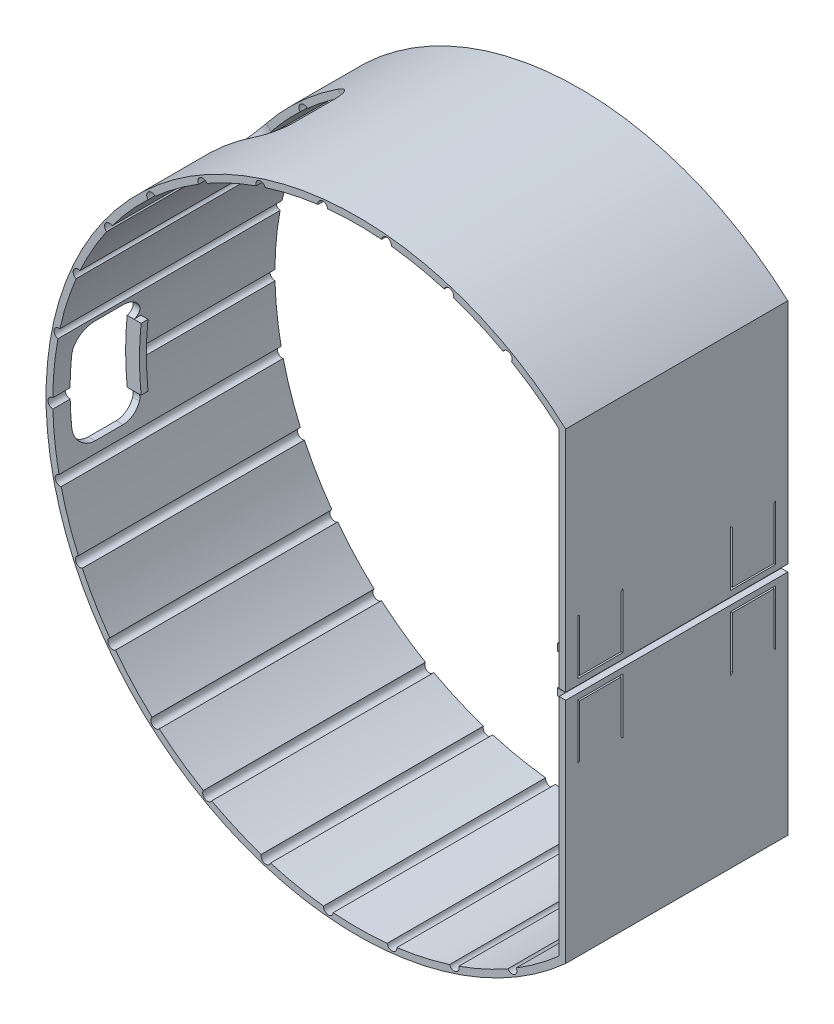
SolidWorks part; units mm, degrees
ref_plane "Front Plane" through (0, 0, 0) normal (1, 0, 0) x (0, 1, 0)
ref_plane "Top Plane" through (0, 0, 0) normal (0, 0, 1) x (0, 1, 0)
ref_plane "Right Plane" through (0, 0, 0) normal (0, 1, 0) x (-1, 0, 0)
sketch "Sketch1" plane through (0, 0, 0) normal (0, 0, 1) x (0, 1, 0)
  line L0 (-66.9026, -60.2) -> (-1, -60.2)
  line L1 (-65.9842, -58.3) -> (-1, -58.3)
  line L2 (-1, -60.2) -> (-1, -58.3)
  line L3 (1, -60.2) -> (1, -58.3)
  line L4 (1, -60.2) -> (66.9026, -60.2)
  line L5 (1, -58.3) -> (65.9842, -58.3)
  arc A0 (66.9026, -60.2) -> (-66.9026, -60.2) centre (0, 0) ccw
  arc A1 (65.9842, -58.3) -> (-65.9842, -58.3) centre (0, 0) ccw
  dimension "D1" = 180
  dimension "D2" = 176.1
  dimension "D3" = 60.2
  dimension "D4" = 1.9
  dimension "D5" = 1
  dimension "D6" = 1
extrude "Boss-Extrude1" add sketch "Sketch1" along normal blind 64.2
sketch "Sketch2" plane through (0, 0, 0) normal (1, 0, 0) x (0, 1, 0)
  line L0 (0, 67.3305) -> (0, -7.6543) construction
ref_plane "Plane1" through (0, 0, 0) normal (0.7071, -0.7071, 0) x (0, 0, -1)
sketch "Sketch3" plane through (0, 0, 0) normal (0.7071, -0.7071, 0) x (0, 0, -1)
  line L0 (-64.2, 87.8822) -> (-64.2, -88.05) construction
  line L1 (-44.2, -16.05) -> (-20.2, -16.05)
  line L2 (-44.2, -16.05) -> (-44.2, 23.95)
  line L3 (-44.2, 23.95) -> (-20.2, 23.95)
  line L4 (-20.2, -16.05) -> (-20.2, 23.95)
  line L6 (-64.2, -88.05) -> (0, -88.05) construction
  dimension "D1" = 40
  dimension "D2" = 24
  dimension "D3" = 20
  dimension "D4" = 72
extrude "Cut-Extrude1" cut sketch "Sketch3" against normal blind 120.2
sketch "Sketch4" plane through (0, 0, 0) normal (1, 0, 0) x (0, 1, 0)
  line L0 (0, 200067.3305) -> (0, -200007.6543) construction
  line L1 (-15, 59.2) -> (15, 59.2)
  line L2 (-15, 59.2) -> (-15, 39.2)
  line L3 (-15, 39.2) -> (15, 39.2)
  line L4 (15, 59.2) -> (15, 39.2)
  line L5 (90, 64.2) -> (-90, 64.2) construction
  dimension "D1" = 15
  dimension "D2" = 15
  dimension "D3" = 20
  dimension "D4" = 5
extrude "Cut-Extrude2" cut sketch "Sketch4" against normal blind 120.2
fillet "Fillet1" radius 6 8 edges at (-43.6939, 77.5643, 44.2) (-73.2676, 50.5695, 44.2) (-73.2676, 50.5695, 20.2) (-43.6939, 77.5643, 20.2) (-87.7521, 15, 39.2) (-87.7521, -15, 39.2) (-87.7521, -15, 59.2) (-87.7521, 15, 59.2)
sketch "Sketch5" plane through (58.3, 0, 0) normal (-1, 0, 0) x (0, -1, 0)
  line L0 (90, 64.2) -> (-90, 64.2) construction
  line L5 (-6.5842, 58.7) -> (-4.5842, 58.7)
  line L6 (-6.5842, 58.7) -> (-6.5842, 49.7)
  line L7 (-6.5842, 49.7) -> (-4.5842, 49.7)
  line L8 (-4.5842, 58.7) -> (-4.5842, 49.7)
  line L9 (-6.5842, 58.7) -> (-4.5842, 49.7) construction
  line L10 (-6.5842, 49.7) -> (-4.5842, 58.7) construction
  line L11 (-65.9842, 64.2) -> (-65.9842, 0) construction
  line L12 (-65.9842, 32.1) -> (65.9842, 32.1) construction
  line L13 (65.9842, 64.2) -> (65.9842, 0) construction
  point P0 (-5.5842, 54.2)
  dimension "D1" = 2
  dimension "D2" = 9
  dimension "D3" = 10
  dimension "D4" = 60.4
extrude "Boss-Extrude2" add sketch "Sketch5" along normal blind 6
sketch "Sketch6" plane through (0, 0, 58.7) normal (0, 0, 1) x (1, 0, 0)
  line L0 (58.3, 6.5842) -> (56.1, 6.5842) construction
  line L1 (52.3, 6.5842) -> (58.3, 6.5842) construction
  line L2 (56.1, 6.5842) -> (56.1, 7.5842)
  line L3 (52.3, 6.5842) -> (56.1, 7.5842)
  line L4 (52.3, 6.5842) -> (56.1, 6.5842)
  dimension "D1" = 1
extrude "Boss-Extrude3" add sketch "Sketch6" against normal blind 9
sketch "Sketch7" plane through (58.3, 0, 0) normal (-1, 0, 0) x (0, -1, 0)
  line L0 (-4.5842, 58.7) -> (-6.5842, 58.7) construction
  line L1 (-18.1626, 60.2) -> (-3.1626, 60.2)
  line L3 (-18.1626, 48.2) -> (-3.1626, 48.2)
  line L4 (-3.1626, 60.2) -> (-3.1626, 48.2)
  line L5 (-18.1626, 60.2) -> (-3.1626, 48.2) construction
  line L6 (-18.1626, 48.2) -> (-3.1626, 60.2) construction
  line L8 (-2.6626, 60.7) -> (-18.6626, 60.7)
  line L9 (-2.6626, 60.7) -> (-2.6626, 47.7)
  line L10 (-2.6626, 47.7) -> (-18.6626, 47.7)
  line L12 (-2.6626, 60.7) -> (-18.6626, 47.7) construction
  line L13 (-2.6626, 47.7) -> (-18.6626, 60.7) construction
  line L14 (-18.1626, 60.2) -> (-18.6626, 60.7)
  line L15 (-18.1626, 48.2) -> (-18.6626, 47.7)
  point P0 (-10.6626, 54.2)
  point P7 (-10.6626, 54.2)
  dimension "D1" = 12
  dimension "D2" = 15
  dimension "D3" = 1.5
  dimension "D4" = 0.5
  dimension "D5" = 0.5
extrude "Cut-Extrude3" cut sketch "Sketch7" against normal blind 9
sketch "Sketch8" plane through (58.3, 0, 0) normal (-1, 0, 0) x (0, -1, 0)
  line L0 (0, 74.2736) -> (0, -25.5173) construction
  line L1 (0, 200067.3305) -> (0, -200007.6543) construction
  line L2 (-65.9842, 32.1) -> (101.8942, 32.1) construction
  line L3 (-65.9842, 64.2) -> (-65.9842, 0) construction
ref_plane "Plane2" through (0, 0, 0) normal (0, 1, 0) x (-1, 0, 0)
ref_plane "Plane3" through (0, 0, 32.1) normal (0, 0, 1) x (0, -1, 0)
mirror "Mirror1" about plane through (0, 0, 0) normal (0, 1, 0) of "Cut-Extrude3", "Boss-Extrude3", "Boss-Extrude2"
mirror "Mirror2" about plane through (0, 0, 32.1) normal (0, 0, 1) of "Mirror1", "Cut-Extrude3", "Boss-Extrude3", "Boss-Extrude2"
sketch "Sketch9" plane through (0, 0, 64.2) normal (0, 0, 1) x (1, 0, 0)
  circle A0 centre (-88.0464, -0.7976) radius 1.4
  arc A1 (58.3, 65.9842) -> (58.3, -65.9842) centre (0, 0) ccw construction
  circle A2 centre (-86.2882, 17.5257) radius 1.4
  circle A3 centre (-80.7588, 35.083) radius 1.4
  circle A4 centre (-71.6998, 51.1071) radius 1.4
  circle A5 centre (-59.5073, 64.8975) radius 1.4
  circle A6 centre (-44.7139, 75.8516) radius 1.4
  circle A7 centre (-27.9664, 83.4906) radius 1.4
  circle A8 centre (-9.9966, 87.4807) radius 1.4
  circle A9 centre (8.4101, 87.6474) radius 1.4
  circle A10 centre (26.4493, 83.9836) radius 1.4
  circle A11 centre (43.3325, 76.6492) radius 1.4
  circle A21 centre (44.7139, -75.8516) radius 1.4
  circle A22 centre (27.9664, -83.4906) radius 1.4
  circle A23 centre (9.9966, -87.4807) radius 1.4
  circle A24 centre (-8.4101, -87.6474) radius 1.4
  circle A25 centre (-26.4493, -83.9836) radius 1.4
  circle A26 centre (-43.3325, -76.6492) radius 1.4
  circle A27 centre (-58.3218, -65.9649) radius 1.4
  circle A28 centre (-70.7622, -52.3976) radius 1.4
  circle A29 centre (-80.11, -36.5403) radius 1.4
  circle A30 centre (-85.9565, -19.086) radius 1.4
  point P66 (0, 0)
  dimension "D1" = 2.8
extrude "Cut-Extrude5" cut sketch "Sketch9" against normal blind 100
sketch "Sketch12" plane through (0, 0, 39.2) normal (0, 0, 1) x (1, 0, 0)
  line L0 (-89.5489, 9) -> (-85.5278, 9)
  line L1 (-89.5489, -9) -> (-85.5278, -9)
  arc A0 (-89.5489, 9) -> (-89.5489, -9) centre (0, 0) ccw
  arc A1 (-85.5278, 9) -> (-85.5278, -9) centre (0, 0) ccw
  dimension "D1" = 172
extrude "Boss-Extrude5" add sketch "Sketch12" along normal blind 2
fillet "Fillet4" radius 2 2 edges at (-88.5688, 9, 39.2) (-88.5688, -9, 39.2)
